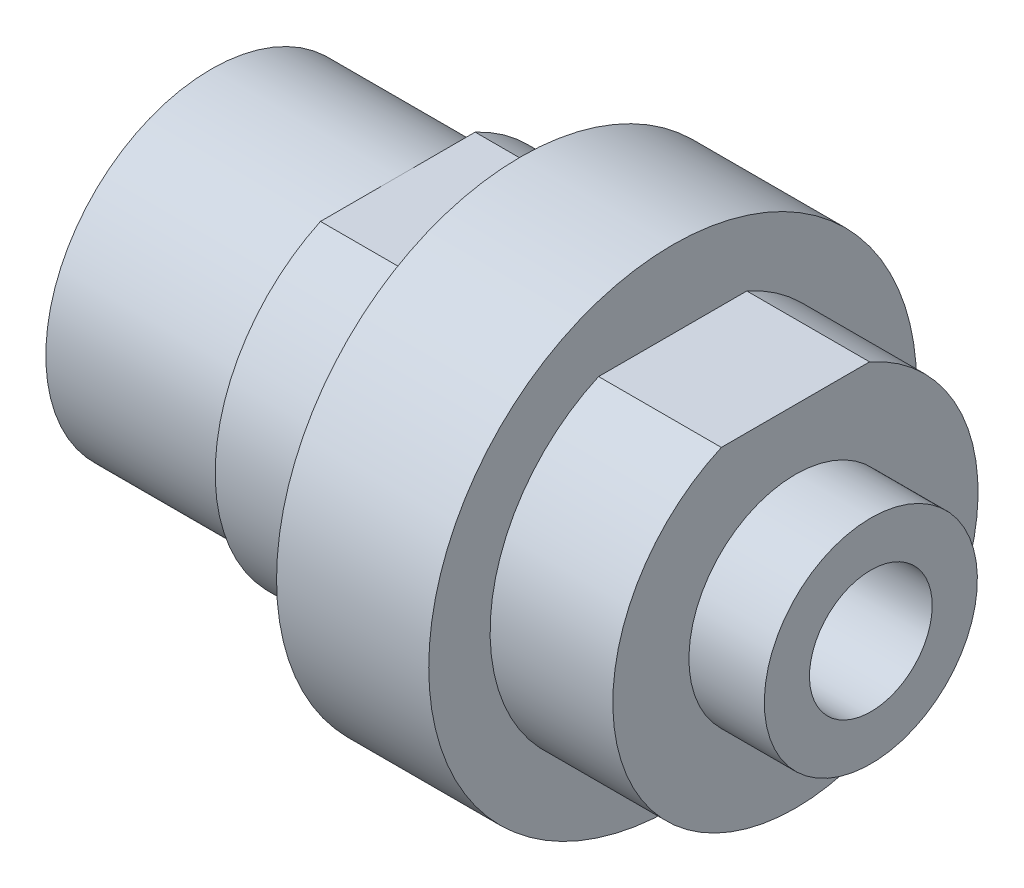
SolidWorks part; units mm, degrees
ref_plane "Front Plane" through (0, 0, 0) normal (0, 0, 1) x (1, 0, 0)
ref_plane "Top Plane" through (0, 0, 0) normal (0, 1, 0) x (1, 0, 0)
ref_plane "Right Plane" through (0, 0, 0) normal (1, 0, 0) x (0, 0, -1)
sketch "Sketch1" plane through (0, 0, 0) normal (0, 0, 1) x (1, 0, 0)
  line L0 (0, 0) -> (0, 8.5598)
  line L1 (0, 8.5598) -> (9.652, 8.5598)
  line L2 (9.652, 8.5598) -> (9.652, 9.4488)
  line L3 (9.652, 9.4488) -> (16.002, 9.4488)
  line L4 (16.002, 9.4488) -> (16.002, 12.6238)
  line L5 (16.002, 12.6238) -> (23.876, 12.6238)
  line L6 (23.876, 12.6238) -> (23.876, 9.4488)
  line L7 (23.876, 9.4488) -> (30.226, 9.4488)
  line L8 (30.226, 9.4488) -> (30.226, 5.5118)
  line L9 (30.226, 5.5118) -> (34.1274, 5.5118)
  line L10 (34.1274, 5.5118) -> (34.1274, 0)
  line L11 (34.1274, 0) -> (0, 0)
  line L12 (34.1274, 3.175) -> (0, 3.175)
  line L13 (34.1274, 0) -> (34.1274, 3.175)
  dimension "D1" = 9.652
  dimension "D2" = 6.35
  dimension "D3" = 7.874
  dimension "D4" = 6.35
  dimension "D5" = 3.9014
  dimension "D6" = 3.937
  dimension "D7" = 3.175
  dimension "D8" = 3.175
  dimension "D9" = 0.889
  dimension "D10" = 8.5598
  dimension "D11" = 3.175
revolve "Revolve1" add sketch "Sketch1" angle 360 about L11 region at (16.807, 6.67, 0)
sketch "Sketch2" plane through (0, 0, 0) normal (0, 0, 1) x (1, 0, 0)
  line L0 (9.652, 9.4488) -> (9.652, 8.5598)
  line L1 (9.652, 8.5598) -> (16.002, 8.5598)
  line L2 (16.002, 9.4488) -> (16.002, -9.4488) construction
  line L3 (16.002, 8.5598) -> (16.002, 9.4488)
  line L4 (16.002, 9.4488) -> (9.652, 9.4488)
  line L5 (23.876, 9.4488) -> (23.876, 8.636)
  line L6 (23.876, 8.636) -> (30.226, 8.636)
  line L7 (30.226, 8.636) -> (30.226, 9.4488)
  line L8 (30.226, 9.4488) -> (23.876, 9.4488)
  point P14 (30.226, 9.4488)
extrude "Cut-Extrude1" cut sketch "Sketch2" against normal through all both and the other way through all
